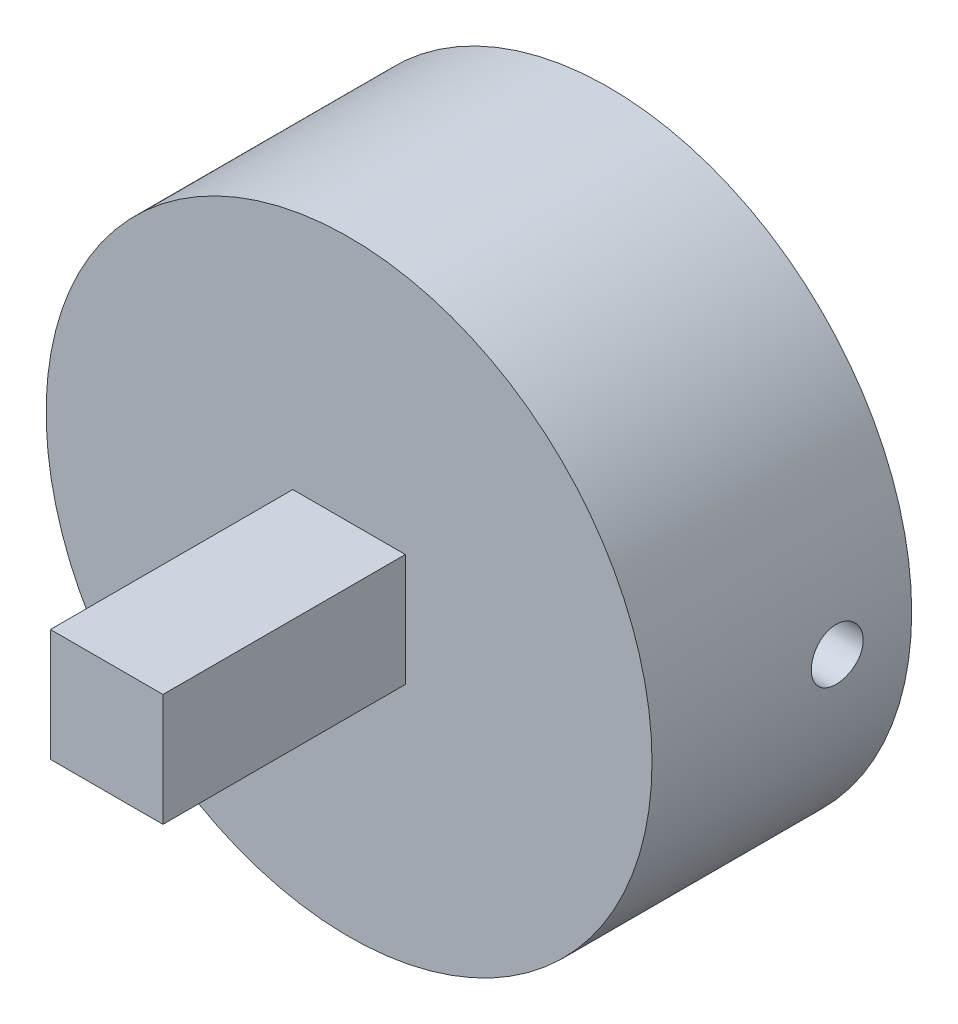
SolidWorks part; units mm, degrees
note: '?' marks a value the reader was unsure of. The reader was unsure of these and kept them because the rebuilt part matched: shared geometry of "Sketch1<3>", "Sketch8<4>".
ref_plane "Front Plane" through (0, 0, 0) normal (0, 0, 1) x (1, 0, 0)
ref_plane "Top Plane" through (0, 0, 0) normal (0, 1, 0) x (1, 0, 0)
ref_plane "Right Plane" through (0, 0, 0) normal (1, 0, 0) x (0, 0, -1)
sketch "Sketch1" plane through (0, 0, 0) normal (0, 0, 1) x (1, 0, 0)
  circle A0 centre (0, 0) radius 2.5
  circle A2 centre (0, 0) radius 2.5 construction
  circle A3 centre (0, 0) radius 17.5
  point P6 (0, 0)
  dimension "D2" = 35
extrude "Boss-Extrude1" add sketch "Sketch1" against normal blind 10 contours A3 A0
extrude "Boss-Extrude2" add sketch "Sketch1<3>" along normal blind 5 contours A3
sketch "Sketch1<3>" plane through (0, 0, 0) normal (0, 0, 1) x (1, 0, 0) same geometry as "Sketch1"
hole_wizard "M3 Clearance Hole1" [suppressed] positions "Sketch6" profile "Sketch7" hole size "M3" standard "ANSI Metric"
sketch "Sketch6" plane through (0, 0, 5) normal (0, 0, 1) x (1, 0, 0)
  point P0 (0, 9)
  point P2 (0, -9)
sketch "Sketch7" plane through (0, 9, 5) normal (1, 0, 0) x (0, -1, 0)
  line L0 (0, 0) -> (0, 5)
  line L1 (0, 5) -> (1.7, 5)
  line L2 (1.7, 5) -> (1.7, 0)
  line L5 (1.7, 0) -> (0, 0)
  line L11 (0, -6.35) -> (0, 107.95) construction
  dimension "Thru Hole Dia." = 3.4
  dimension "Thru Hole Depth" = 5
ref_plane "Plane1" through (2.5, 0, 0) normal (1, 0, 0) x (0, 0, -1)
ref_plane "Plane2" through (5.5, 0, 0) normal (1, 0, 0) x (0, 0, -1)
sketch "Sketch8" plane through (5.5, 0, 0) normal (1, 0, 0) x (0, 0, -1)
  line L0 (10, 0) -> (5.7, 0) construction
  line L1 (8.5, 2.8) -> (2.9, 2.8)
  line L3 (8.5, -2.8) -> (2.9, -2.8)
  line L4 (2.9, 2.8) -> (2.9, -2.8)
  line L5 (10, -17.5) -> (10, 17.5) construction
  line L6 (5.7, 2.8) -> (5.7, -2.8) construction
  line L7 (8.5, 2.8) -> (10, 2.8)
  line L8 (8.5, -2.8) -> (10, -2.8)
  line L9 (10, 2.8) -> (10, -2.8)
  circle A0 centre (5.7, 0) radius 1.5
  dimension "D4" = 3
  dimension "D1" = 5.6
  dimension "D2" = 5.6
  dimension "D3" = 1.5
extrude "Cut-Extrude1" cut sketch "Sketch8" along normal up to next and the other way up to next contours A0
extrude "Cut-Extrude2" cut sketch "Sketch8<4>" along normal blind 2.2 contours L1 L4 L3 L8 L9 L7
sketch "Sketch8<4>" plane through (5.5, 0, 0) normal (1, 0, 0) x (0, 0, -1) same geometry as "Sketch8"
ref_axis "Axis1" through (0, 0, -57.5) along (0, 0, 1)?
ref_plane "Mirror Plane" through (0, 0, 0) normal (1, 0, 0) x (0, 0, -1)
mirror "Mirror1" about plane through (0, 0, 0) normal (1, 0, 0) of "Cut-Extrude2", "Cut-Extrude1"
sketch "Sketch10" plane through (0, 0, 5) normal (0, 0, 1) x (1, 0, 0)
  line L1 (-3.25, 3.25) -> (3.25, 3.25)
  line L2 (-3.25, 3.25) -> (-3.25, -3.25)
  line L3 (-3.25, -3.25) -> (3.25, -3.25)
  line L4 (3.25, 3.25) -> (3.25, -3.25)
  line L5 (-3.25, 3.25) -> (3.25, -3.25) construction
  line L6 (-3.25, -3.25) -> (3.25, 3.25) construction
  point P0 (0, 0)
  dimension "D1" = 6.5
extrude "Boss-Extrude3" add sketch "Sketch10" along normal blind 14
